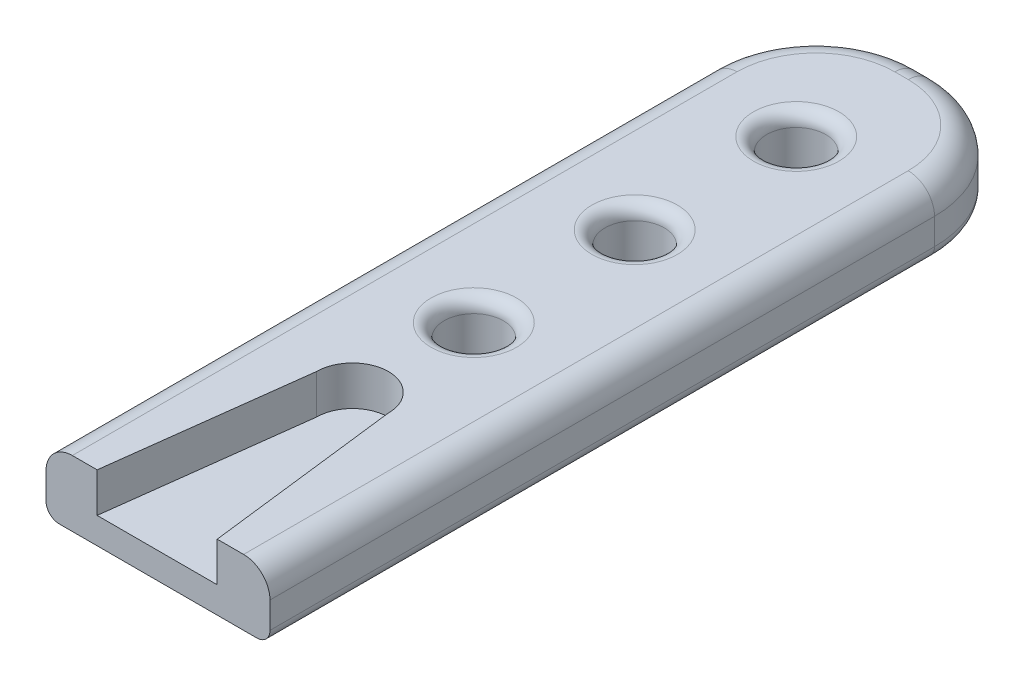
SolidWorks part; units mm, degrees
ref_plane "Front Plane" through (0, 0, 0) normal (0, 0, 1) x (1, 0, 0)
ref_plane "Top Plane" through (0, 0, 0) normal (0, 1, 0) x (1, 0, 0)
ref_plane "Right Plane" through (0, 0, 0) normal (1, 0, 0) x (0, 0, -1)
sketch "Sketch2" plane through (0, 0, 0) normal (0, 1, 0) x (1, 0, 0)
  line L0 (-2.8871, -33.135) -> (-4.752, -47.945)
  line L1 (4.3722, -47.945) -> (2.5735, -33.1417)
  line L3 (-8.637, -47.945) -> (-4.752, -47.945)
  line L4 (-8.637, 10.5542) -> (8.3807, 10.5542)
  line L5 (-8.637, 10.5542) -> (-8.637, -47.945)
  line L6 (8.3807, 10.6437) -> (8.3807, 10.5542)
  line L7 (4.3722, -47.945) -> (8.3807, -47.945)
  line L8 (-8.637, -47.945) -> (8.3807, -47.945)
  line L9 (8.3807, 10.5542) -> (8.3807, -47.945)
  line L10 (-8.637, 10.5542) -> (8.3807, 10.5542)
  line L11 (-8.637, -47.945) -> (8.3807, -47.945)
  line L12 (-0.1284, 10.5542) -> (-0.1284, 10.6437)
  line L14 (8.3807, 10.5542) -> (8.3807, 10.6437)
  line L15 (-0.1284, 10.5542) -> (-0.1284, 10.6437)
  arc A0 (-2.8871, -33.135) -> (2.5735, -33.1417) centre (-0.1568, -33.1384) cw
  circle A3 centre (-0.1283, 0.5542) radius 2.25
  circle A4 centre (-0.1284, -11.7215) radius 2.25
  circle A5 centre (-0.1284, -23.9474) radius 2.25
  dimension "D1" = 4.5
extrude "Boss-Extrude1" add sketch "Sketch2" along normal blind 2 contours L0 A0 L1 L7 L9 L10 L4 L5 L3 A5 A4 A3 | A0 L0 L8 L1 region at (-0.1732, 0, 40.2633) region at (-0.1217, 0, 15.9811)
extrude "Boss-Extrude2" add sketch "Sketch2<7>" along normal blind 5 contours L0 A0 L1 L7 L9 L10 L4 L5 L3 A5 A4 A3 region at (-0.1217, 0, 15.9811)
sketch "Sketch2<7>" plane through (0, 0, 0) normal (0, 1, 0) x (1, 0, 0) same geometry as "Sketch2"
fillet "Fillet1" radius 8 2 edges at (-8.637, 2.5, -10.5542) (8.3807, 2.5, -10.5542)
fillet "Fillet2" radius 2 5 edges at (8.3807, 5, 22.6954) (6.0375, 5, -8.2111) (-0.1282, 5, -10.5542) (-6.2939, 5, -8.2111) (-8.637, 5, 22.6954)
fillet "Fillet3" radius 1 6 edges at (-0.1284, 0, 26.1974) (-0.1284, 0, 13.9715) (-0.1283, 0, 1.6958) (-0.1283, 5, 1.6958) (-0.1284, 5, 13.9715) (-0.1284, 5, 26.1974)
fillet "Fillet4" radius 1 5 edges at (-8.637, 0, 22.6954) (-6.2939, 0, -8.2111) (-0.1282, 0, -10.5542) (6.0375, 0, -8.2111) (8.3807, 0, 22.6954)
